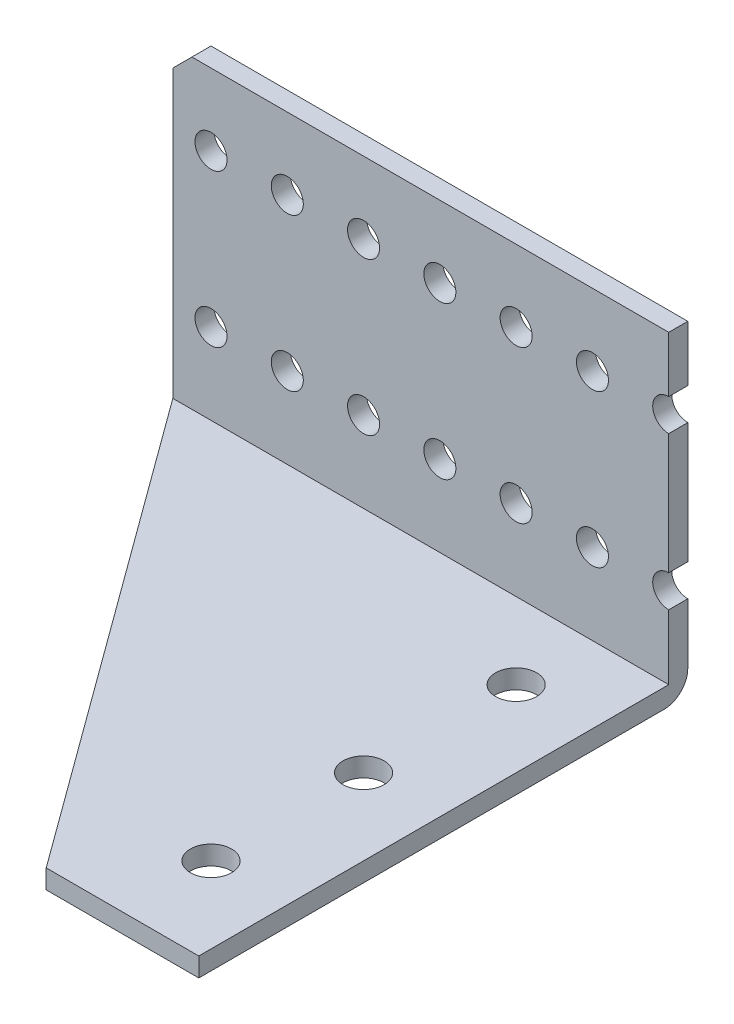
SolidWorks part; units mm, degrees
ref_plane "Front Plane" through (0, 0, 0) normal (0, 0, 1) x (1, 0, 0)
ref_plane "Top Plane" through (0, 0, 0) normal (0, 1, 0) x (1, 0, 0)
ref_plane "Right Plane" through (0, 0, 0) normal (1, 0, 0) x (0, 0, -1)
sketch "Sketch1" plane through (0, 0, 0) normal (0, 1, 0) x (1, 0, 0)
  line L0 (41.275, -40.7035) -> (41.275, 40.7035)
  line L1 (41.275, 40.7035) -> (-41.275, 40.7035)
  line L3 (-41.275, -40.7035) -> (-41.275, 40.7035)
  line L4 (-41.275, -40.7035) -> (41.275, -40.7035)
  line L5 (41.275, 40.7035) -> (-41.275, -40.7035) construction
  line L6 (0, -55) -> (0, 55) construction
  line L7 (-55, 0) -> (55, 0) construction
  point P2 (0, 0)
  dimension "D2" = 81.407
  dimension "D1" = 82.55
extrude "Boss-Extrude1" add sketch "Sketch1" along normal blind 3.175 from offset 34.925 offset against normal yes
sketch "Sketch3" plane through (0, -31.75, 0) normal (0, 1, 0) x (1, 0, 0)
  line L0 (41.275, 37.5285) -> (-41.275, 37.5285)
  line L1 (-41.275, 37.5285) -> (-41.275, 40.7035)
  line L2 (-41.275, 40.7035) -> (41.275, 40.7035)
  line L4 (41.275, 37.5285) -> (41.275, 40.7035)
  line L5 (-41.275, 40.7035) -> (-41.275, -40.7035) construction
  line L6 (41.275, -40.7035) -> (41.275, 40.7035) construction
  line L7 (41.275, 40.7035) -> (-41.275, 40.7035) construction
  dimension "D1" = 3.175
extrude "Boss-Extrude2" add sketch "Sketch3" along normal blind 50.8
hole_wizard "#10 Clearance Hole2" positions "Sketch7" profile "Sketch6" hole size "#10" standard "ANSI Inch" end condition through all
sketch "Sketch7" plane through (0, 0, -40.7035) normal (0, 0, -1) x (-1, 0, 0)
  line L2 (-41.275, -18.288) -> (34.925, -18.288) construction
  line L5 (-41.275, 7.112) -> (34.925, 7.112) construction
  line L8 (41.275, 19.05) -> (41.275, -34.925) construction
  line L9 (-41.275, 19.05) -> (-41.275, -34.925) construction
  line L10 (-41.275, 19.05) -> (41.275, 19.05) construction
  point P56 (22.225, 7.112)
  point P57 (9.525, 7.112)
  point P58 (-3.175, 7.112)
  point P59 (-15.875, 7.112)
  point P61 (-28.575, 7.112)
  point P118 (22.225, -18.288)
  point P119 (9.525, -18.288)
  point P120 (-3.175, -18.288)
  point P121 (-15.875, -18.288)
  point P123 (-28.575, -18.288)
  point P157 (34.925, 7.112)
  point P159 (34.925, -18.288)
  point P185 (-41.275, 7.112)
  point P189 (-41.275, -18.288)
  dimension "D1" = 6.35
  dimension "D2" = 11.938
  dimension "D3" = 12.7
  dimension "D4" = 25.4
  dimension "D5" = 12.7
  dimension "D6" = 12.7
  dimension "D7" = 12.7
  dimension "D8" = 12.7
  dimension "D10" = 12.7
sketch "Sketch6" plane through (-22.225, 7.112, -40.7035) normal (1, 0, 0) x (0, 1, 0)
  line L0 (0, 0) -> (0, 81.407)
  line L1 (0, 81.407) -> (2.667, 81.407)
  line L2 (2.667, 81.407) -> (2.667, 0)
  line L5 (2.667, 0) -> (0, 0)
  line L11 (0, -6.35) -> (0, 107.95) construction
  dimension "Thru Hole Dia." = 5.334
  dimension "Thru Hole Depth" = 81.407
chamfer "Chamfer1" distance 3.175 angle 45 1 edges at (-41.275, 19.05, -39.116)
fillet "Fillet2" radius 3.937 1 edges at (0, -34.925, -40.7035) tangent propagation no
sketch "Sketch9" plane through (0, -34.925, 0) normal (0, -1, 0) x (1, 0, 0)
  line L2 (41.275, -40.7035) -> (-41.275, -40.7035) construction
  line L3 (41.275, 40.7035) -> (41.275, -36.7665) construction
  line L5 (-41.275, -37.5285) -> (-41.275, 40.7035)
  line L6 (-41.275, 40.7035) -> (41.275, 40.7035) construction
  line L7 (28.575, -40.7035) -> (28.575, 40.7035) construction
  line L10 (-41.275, -37.5285) -> (15.875, 40.7035)
  line L11 (15.875, 40.7035) -> (-41.275, 40.7035)
  line L12 (41.275, 40.7035) -> (41.275, -36.7665) construction
  line L14 (-41.275, -36.7665) -> (-41.275, 40.7035) construction
  line L16 (-41.275, -37.5285) -> (41.275, -37.5285) construction
  circle A0 centre (34.925, 1.4605) radius 3.429 construction
  circle A1 centre (34.925, -11.2395) radius 3.429 construction
  circle A2 centre (34.925, -23.9395) radius 3.429 construction
  circle A3 centre (28.575, -24.8285) radius 3.429
  circle A7 centre (28.575, 0.5715) radius 3.429
  circle A8 centre (28.575, 25.9715) radius 3.429
  point P1 (-41.275, 36.8409)
  point P2 (-41.275, 36.8409)
  point P3 (-41.275, 36.8409)
  point P8 (0, 0)
  point P17 (0, 0)
  point P18 (-41.275, 36.8409)
  point P21 (28.1738, 40.7035)
  point P27 (0, 0)
  point P32 (-41.275, 36.8409)
  point P33 (0, 0)
  point P34 (0, 0)
  point P35 (0, 0)
  point P36 (0, 0)
  point P37 (-41.275, -36.7665)
  point P38 (0, 0)
  point P39 (0, 0)
  point P40 (0, 0)
  point P41 (28.8628, 36.8409)
  point P42 (0, 0)
  point P46 (0, 0)
  point P49 (-41.275, -40.7035)
  dimension "D3" = 6.858
  dimension "D7" = 16.764
  dimension "D9" = 6.858
  dimension "D10" = 0
  dimension "D11" = 3
  dimension "D12" = 25.4
  dimension "D2" = 12.7
  dimension "D4" = 12.7
  dimension "D5" = 12.7
  dimension "D6" = 6.35
  dimension "D8" = 25.4
  dimension "D13" = 12.7
extrude "Cut-Extrude2" cut sketch "Sketch9" against normal through all
